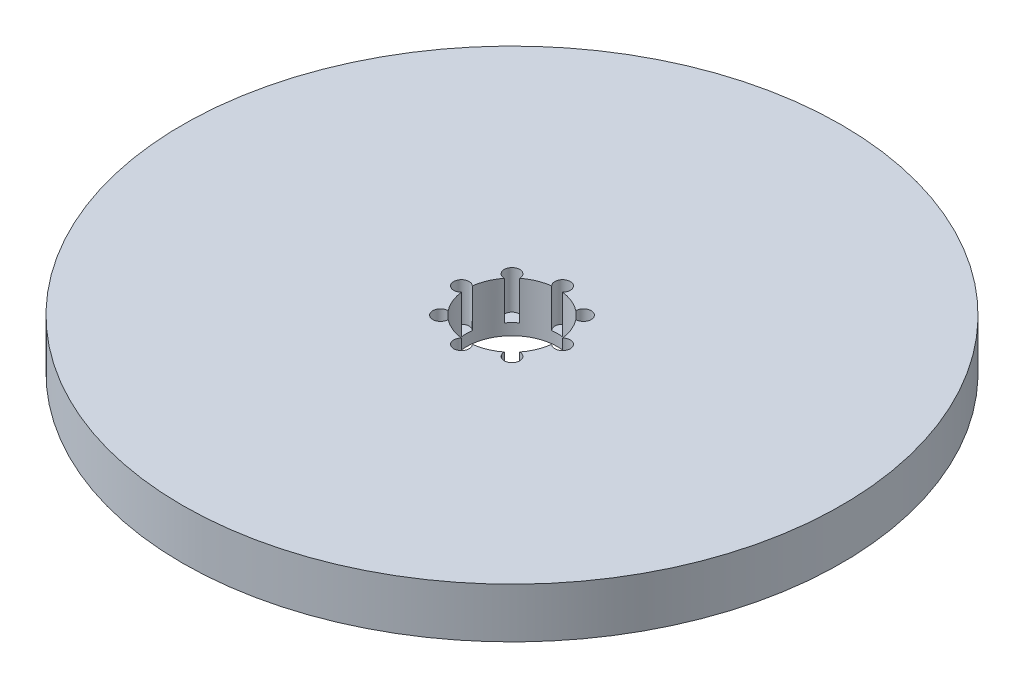
SolidWorks part; units mm, degrees
ref_plane "Front Plane" through (0, 0, 0) normal (0, 0, 1) x (1, 0, 0)
ref_plane "Top Plane" through (0, 0, 0) normal (0, 1, 0) x (1, 0, 0)
ref_plane "Right Plane" through (0, 0, 0) normal (1, 0, 0) x (0, 0, -1)
sketch "Sketch1" plane through (0, 0, 0) normal (0, 1, 0) x (1, 0, 0)
  circle A0 centre (0, 0) radius 72.5
  dimension "FLANGE_OD" = 145
extrude "Boss-Extrude1" add sketch "Sketch1" along normal blind 11
sketch "Sketch2" plane through (0, 0, 0) normal (0, 1, 0) x (1, 0, 0)
  circle A0 centre (0, 0) radius 10
  dimension "BORE_D" = 20
extrude "Cut-Extrude1" cut sketch "Sketch2" along normal through all
sketch "Sketch3" plane through (0, 11, 0) normal (0, 1, 0) x (1, 0, 0)
  circle A0 centre (0, 0) radius 11.1253 construction
  circle A1 centre (-11.1253, 0) radius 1.6938
  dimension "BOLT_D" = 3.3876
  dimension "BOLT_PCD" = 22.2506
extrude "Cut-Extrude2" cut sketch "Sketch3" against normal blind 8.4976
pattern_circular "CirPattern1" count 8 over 360 about axis through (0, 0, 0) along (0, 1, 0) of "Cut-Extrude2"
